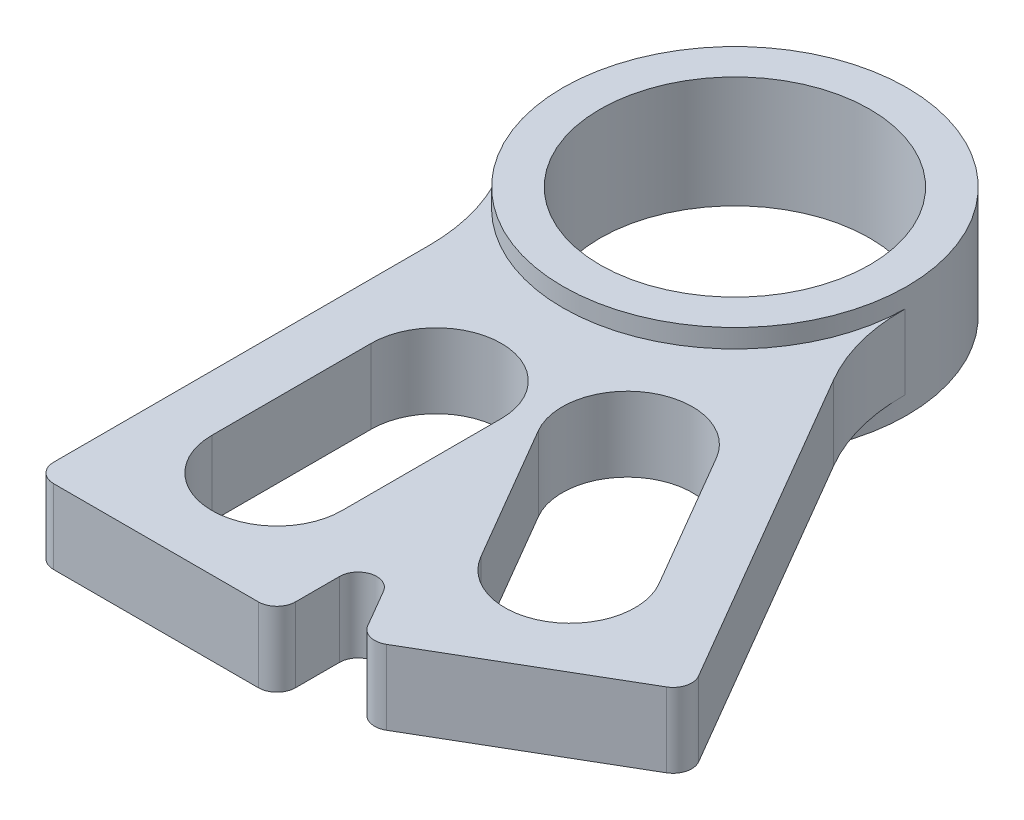
SolidWorks part; units mm, degrees
ref_plane "Front Plane" through (0, 0, 0) normal (0, 0, 1) x (1, 0, 0)
ref_plane "Top Plane" through (0, 0, 0) normal (0, 1, 0) x (1, 0, 0)
ref_plane "Right Plane" through (0, 0, 0) normal (1, 0, 0) x (0, 0, -1)
sketch "Sketch1" plane through (0, 0, 0) normal (0, 1, 0) x (1, 0, 0)
  line L0 (0, 0) -> (0, -49.3903) construction
  line L1 (0, 0) -> (24.8801, -42.666) construction
  line L2 (0, -39.0716) -> (0, -25.4826) construction
  line L3 (-5.5562, -39.0716) -> (-5.5562, -25.4826)
  line L4 (5.5563, -39.0716) -> (5.5563, -25.4826)
  line L5 (19.6821, -33.7521) -> (12.8367, -22.0132) construction
  line L6 (14.8823, -36.551) -> (8.0369, -24.8121)
  line L7 (24.4818, -30.9531) -> (17.6365, -19.2142)
  line L8 (0, -49.3903) -> (0, -44.6278) construction
  line L9 (24.8801, -42.666) -> (22.481, -38.5519) construction
  line L10 (-10.3187, -49.3903) -> (10.3188, -49.3903)
  line L11 (15.9662, -47.864) -> (33.794, -37.4679)
  line L12 (-10.3187, -49.3903) -> (-10.3187, -10.4432)
  line L13 (10.3188, -49.3903) -> (10.3188, -38.1794)
  line L14 (33.794, -37.4679) -> (14.1746, -3.8234)
  line L15 (15.9662, -47.864) -> (10.3188, -38.1794)
  line L16 (178.5686, -306.221) -> (20.548, -35.237) construction
  line L22 (0, 0) -> (10.3188, -38.1794) construction
  circle A0 centre (0, 0) radius 11.5062
  circle A1 centre (0, 0) radius 14.6812
  arc A2 (-5.5562, -39.0716) -> (5.5563, -39.0716) centre (0, -39.0716) ccw
  arc A3 (5.5563, -25.4826) -> (-5.5562, -25.4826) centre (0, -25.4826) ccw
  arc A4 (14.8823, -36.551) -> (24.4818, -30.9531) centre (19.6821, -33.7521) ccw
  arc A5 (17.6365, -19.2142) -> (8.0369, -24.8121) centre (12.8367, -22.0132) ccw
  point P8 (0, -32.2771)
  point P13 (16.2594, -27.8826)
  point P25 (0, -49.3903)
  point P27 (24.8801, -42.666)
  dimension "D2" = 29.3624
  dimension "D3" = 4.7625
  dimension "D4" = 4.7625
  dimension "D5" = 13.589
  dimension "D6" = 49.3903
  dimension "D7" = 20.6375
extrude "Bearing_Insert_Extrude" add sketch "Sketch1" along normal mid plane 9.525 contours A1 A0 region at (-5.4988, 0, -13.1636)
extrude "Apex_Slot_Insert_Extrude" add sketch "Sketch1<4>" along normal mid plane 6.35 contours A1 L12 L10 L13 L15 L11 L14 A5 L7 A4 L6 A3 L4 A2 L3 region at (8.1875, 0, 30.2936)
sketch "Sketch1<4>" plane through (0, 0, 0) normal (0, 1, 0) x (1, 0, 0) same geometry as "Sketch1"
fillet "Fillet1" radius 16.002 2 edges at (14.1746, 0, 3.8234) (-10.3187, 0, 10.4432)
fillet "Fillet2" radius 1.5875 5 edges at (33.794, 0, 37.4679) (15.9662, 0, 47.864) (10.3188, 0, 38.1794) (10.3188, 0, 49.3903) (-10.3187, 0, 49.3903)
equation "\"Apex_thickness\"= .25"
equation "\"Bearing_diameter\"= 0.906in"
equation "\"A-arm_angle\"= 39.1893"
equation "\"D1@Sketch1\"=\"Bearing_diameter\""
equation "\"D1@Apex_Slot_Insert_Extrude\"=\"Apex_thickness\""
